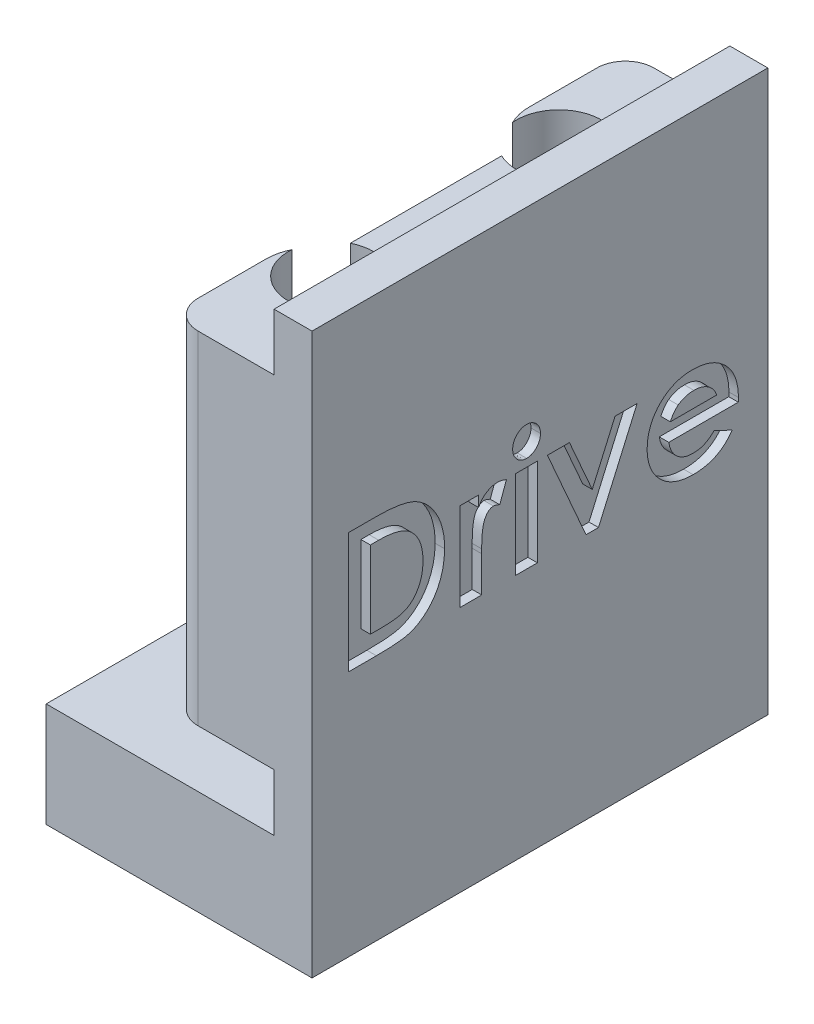
SolidWorks part; units mm, degrees
ref_plane "Front" through (0, 0, 0) normal (0, 0, 1) x (1, 0, 0)
ref_plane "Top" through (0, 0, 0) normal (0, 1, 0) x (1, 0, 0)
ref_plane "Right" through (0, 0, 0) normal (1, 0, 0) x (0, 0, -1)
sketch "Sketch1" plane through (0, 0, 0) normal (0, 1, 0) x (1, 0, 0)
  line L5 (-6, -12) -> (6, -12)
  line L6 (-6, -12) -> (-6, 12)
  line L7 (-6, 12) -> (6, 12)
  line L8 (6, -12) -> (6, 12)
  line L9 (-6, -12) -> (6, 12) construction
  line L10 (-6, 12) -> (6, -12) construction
  point P0 (0, 0)
  dimension "D1" = 12
  dimension "D2" = 24
extrude "Boss-Extrude1" add sketch "Sketch1" along normal blind 5.5
sketch "Sketch2" plane through (0, 0, 0) normal (0, 1, 0) x (1, 0, 0)
  line L0 (6, 12) -> (-6, 12) construction
  line L1 (6, -12) -> (8, -12)
  line L2 (6, -12) -> (6, 12)
  line L3 (6, 12) -> (8, 12)
  line L4 (8, -12) -> (8, 12)
  dimension "D1" = 2
extrude "Boss-Extrude2" add sketch "Sketch2" along normal blind 29.5
sketch "Sketch4" plane through (0, 5.5, 0) normal (0, 1, 0) x (1, 0, 0)
  line L1 (6, -12) -> (0.5, -12)
  line L2 (6, -12) -> (6, 12)
  line L3 (6, 12) -> (0.5, 12)
  line L4 (0.5, -12) -> (0.5, 12)
  line L5 (6, 12) -> (-6, 12) construction
  dimension "D1" = 5.5
extrude "Boss-Extrude4" add sketch "Sketch4" along normal blind 18 from offset 3
sketch "Sketch5" plane through (0.5, 0, 0) normal (-1, 0, 0) x (0, 0, 1)
  line L0 (-12, 26.5) -> (12, 26.5) construction
  line L1 (-4.625, 26.5) -> (4.625, 26.5)
  line L2 (-4.625, 26.5) -> (-4.625, 8.5)
  line L3 (-4.625, 8.5) -> (4.625, 8.5)
  line L4 (4.625, 26.5) -> (4.625, 8.5)
  line L5 (-12, 8.5) -> (12, 8.5) construction
  line L8 (4.625, 26.5) -> (12, 26.5) construction
  line L9 (-4.625, 26.5) -> (-12, 26.5) construction
  dimension "D1" = 9.25
extrude "Cut-Extrude1" cut sketch "Sketch5" against normal blind 1.5
fillet "Fillet1" radius 2.5 2 edges at (0.5, 17.5, 4.625) (0.5, 17.5, -4.625)
sketch "Sketch6" plane through (0, 26.5, 0) normal (0, 1, 0) x (1, 0, 0)
  line L1 (6, -12) -> (6, 12) construction
  line L3 (3, -12) -> (3, -6) construction
  line L4 (0.5, -12) -> (6, -12) construction
  line L5 (3, -6) -> (6, -6) construction
  line L7 (3, 12) -> (3, 6) construction
  line L9 (3, 6) -> (6, 6) construction
  line L10 (6, 12) -> (0.5, 12) construction
  circle A0 centre (3, -6) radius 2.25
  circle A4 centre (3, 6) radius 2.25
  dimension "D3" = 4.5
  dimension "D8" = 4.5
  dimension "D1" = 6
  dimension "D2" = 3
  dimension "D6" = 6
  dimension "D7" = 3
extrude "Cut-Extrude2" cut sketch "Sketch6" against normal through all
fillet "Fillet2" radius 1.5 2 edges at (0.5, 17.5, -12) (0.5, 17.5, 12)
sketch "Sketch7" plane through (8, 0, 0) normal (1, 0, 0) x (0, 0, -1)
  line L0 (-12, 29.5) -> (-12, 0) construction
  line L1 (-12, 0) -> (12, 0) construction
  text T0 "<b>Drive</b>"
  point P1 (-11.2045, 14.2797)
  point P6 (-10.8, 13)
  dimension "D1" = 1.2
  dimension "D2" = 13
extrude "Cut-Extrude3" cut sketch "Sketch7" against normal blind 0.5
